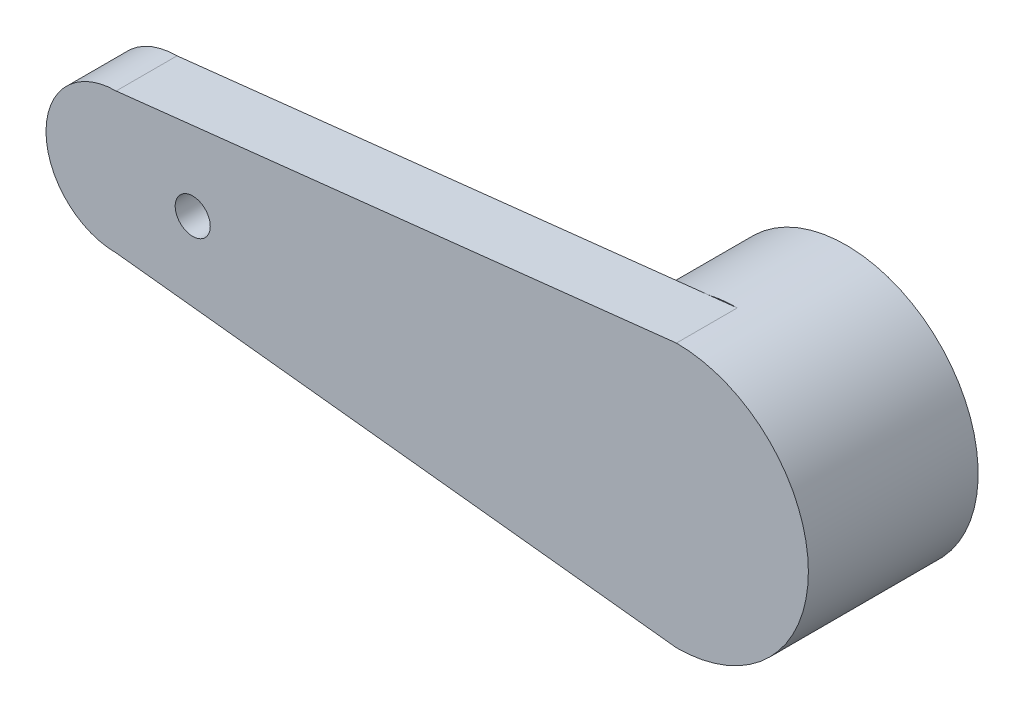
SolidWorks part; units mm, degrees
ref_plane "Front Plane" through (0, 0, 0) normal (0, 0, 1) x (1, 0, 0)
ref_plane "Top Plane" through (0, 0, 0) normal (0, 1, 0) x (1, 0, 0)
ref_plane "Right Plane" through (0, 0, 0) normal (1, 0, 0) x (0, 0, -1)
sketch "Sketch1" plane through (0, 0, 0) normal (0, 0, 1) x (1, 0, 0)
  line L0 (-18.4729, 0) -> (17.4394, 0) construction
  line L1 (-15.1788, 1.9) -> (0, 3.575)
  line L2 (-15.1788, -1.9) -> (0, -3.575)
  arc A0 (0, -3.575) -> (0, 3.575) centre (0, 0) ccw
  arc A1 (-15.1788, 1.9) -> (-15.1788, -1.9) centre (-15.1788, 0) ccw
  dimension "D1" = 7.15
  dimension "D2" = 3.8
extrude "Boss-Extrude1" add sketch "Sketch1" along normal blind 1.65
sketch "Sketch2" plane through (0, 0, 0) normal (0, 0, -1) x (-1, 0, 0)
  circle A0 centre (0, 0) radius 3.575
extrude "Boss-Extrude2" add sketch "Sketch2" along normal blind 2.95
sketch "Sketch3" plane through (0, 0, -2.95) normal (0, 0, -1) x (-1, 0, 0)
  circle A0 centre (0, 0) radius 2.3
  dimension "D1" = 4.6
extrude "Cut-Extrude1" cut sketch "Sketch3" against normal blind 2.95
sketch "Sketch4" plane through (0, 0, 1.65) normal (0, 0, 1) x (1, 0, 0)
  line L0 (-18.8263, 0) -> (7.2668, 0) construction
  circle A0 centre (-13.1038, 0) radius 0.475
  arc A1 (-15.1788, 1.9) -> (-15.1788, -1.9) centre (-15.1788, 0) ccw construction
  dimension "D1" = 0.95
  dimension "D2" = 2.075
extrude "Cut-Extrude2" cut sketch "Sketch4" against normal up to surface (1.65 mm away) up to face at (-9.153, 0, 0)
